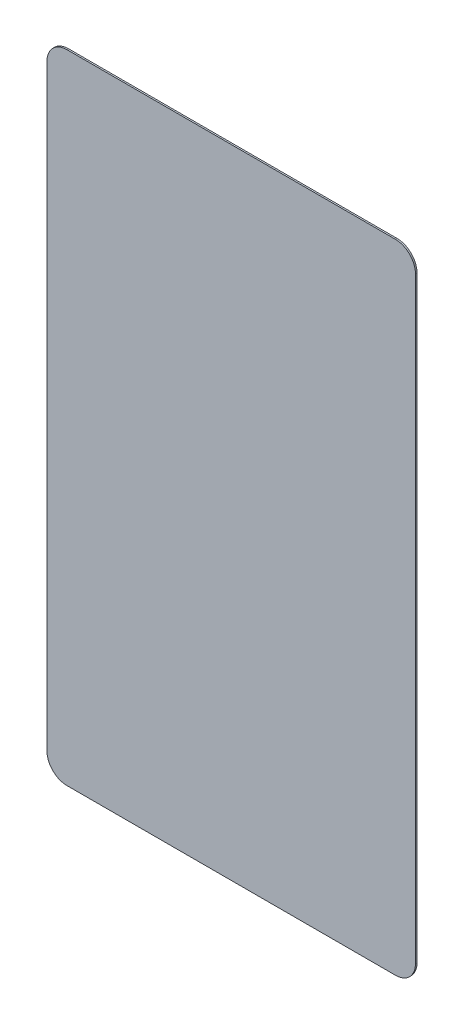
SolidWorks part; units mm, degrees
ref_plane "Front" through (0, 0, 0) normal (0, 0, 1) x (1, 0, 0)
ref_plane "Top" through (0, 0, 0) normal (0, 1, 0) x (1, 0, 0)
ref_plane "Right" through (0, 0, 0) normal (1, 0, 0) x (0, 0, -1)
ref_axis "X Axis" through (-32.3056, 0, 0) along (1, 0, 0)
ref_axis "Y Axis" through (0, -5.08, 0) along (0, 1, 0)
ref_axis "Z Axis" through (0, 0, -0.0127) along (0, 0, -1)
sketch "Sketch1" plane through (0, 0, 0) normal (0, 0, 1) x (1, 0, 0)
  line L0 (-26.1937, 101.6) -> (26.1938, 101.6)
  line L1 (-29.3687, 98.425) -> (-29.3687, 3.175)
  line L2 (-26.1937, 0) -> (26.1938, 0)
  line L3 (29.3688, 98.425) -> (29.3688, 3.175)
  arc A0 (-29.3687, 3.175) -> (-26.1937, 0) centre (-26.1937, 3.175) ccw
  arc A1 (26.1938, 0) -> (29.3688, 3.175) centre (26.1938, 3.175) ccw
  arc A2 (29.3688, 98.425) -> (26.1938, 101.6) centre (26.1938, 98.425) ccw
  arc A3 (-26.1937, 101.6) -> (-29.3687, 98.425) centre (-26.1937, 98.425) ccw
extrude "Boss-Extrude1" add sketch "Sketch1" against normal blind 0.254
